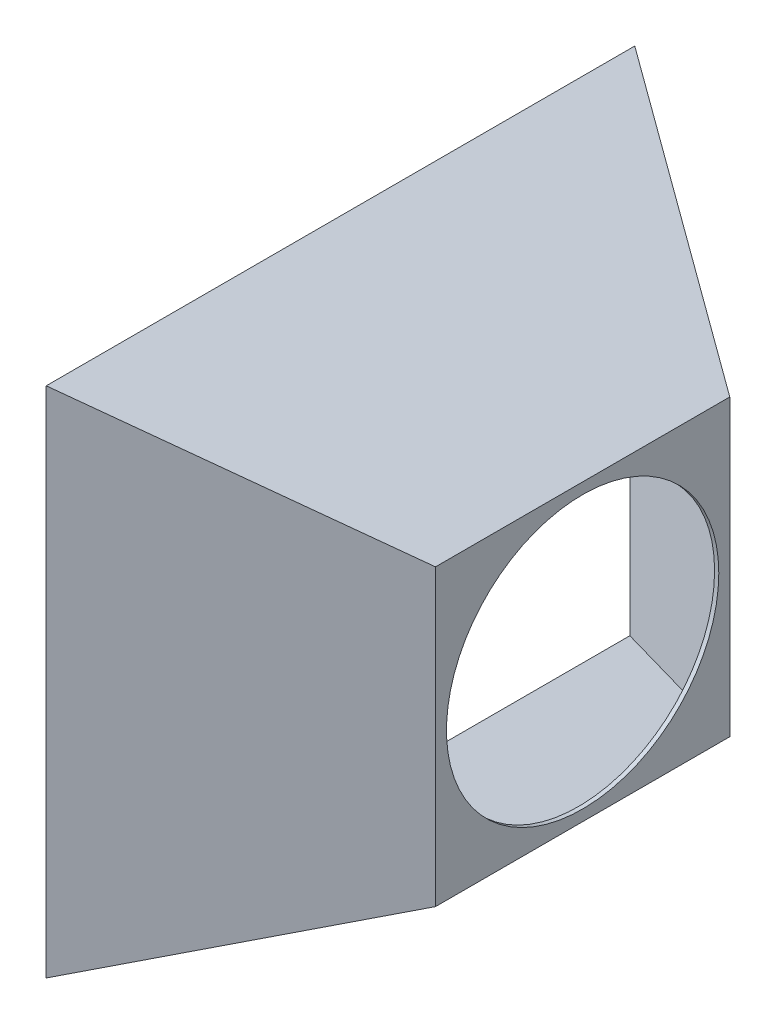
SolidWorks part; units mm, degrees
note: '?' marks a value the reader was unsure of.
ref_plane "Front Plane" through (0, 0, 0) normal (0, 0, 1) x (1, 0, 0)
ref_plane "Top Plane" through (0, 0, 0) normal (0, 1, 0) x (1, 0, 0)
ref_plane "Right Plane" through (0, 0, 0) normal (1, 0, 0) x (0, 0, -1)
sketch "Sketch1" plane through (0, 0, 0) normal (1, 0, 0) x (0, 0, -1)
  line L1 (350, -305) -> (-350, -305)
  line L2 (350, -305) -> (350, 305)
  line L3 (350, 305) -> (-350, 305)
  line L4 (-350, -305) -> (-350, 305)
  line L5 (350, -305) -> (-350, 305) construction
  line L6 (350, 305) -> (-350, -305) construction
  point P0 (0, 0)
ref_plane "Plane1" through (288, 0, 0) normal (1, 0, 0) x (0, 0, -1)
sketch "Sketch2" plane through (288, 0, 0) normal (1, 0, 0) x (0, 0, -1)
  line L1 (175, -175) -> (-175, -175)
  line L2 (175, -175) -> (175, 175)
  line L3 (175, 175) -> (-175, 175)
  line L4 (-175, -175) -> (-175, 175)
  line L5 (175, -175) -> (-175, 175) construction
  line L6 (175, 175) -> (-175, -175) construction
  point P0 (0, 0)
loft "Loft1" add profiles "Sketch1", "Sketch2"
shell "Shell1" thickness 5
sketch "Sketch3" plane through (288, 0, 0) normal (1, 0, 0) x (0, 0, -1)
  circle A0 centre (0, 0) radius 161.95
  dimension "D1" = 323.9
extrude "Cut-Extrude1" cut sketch "Sketch3" against normal blind 10
ref_axis "Axis1" through (227.5096, 0, 0) along (1, 0, 0)?
